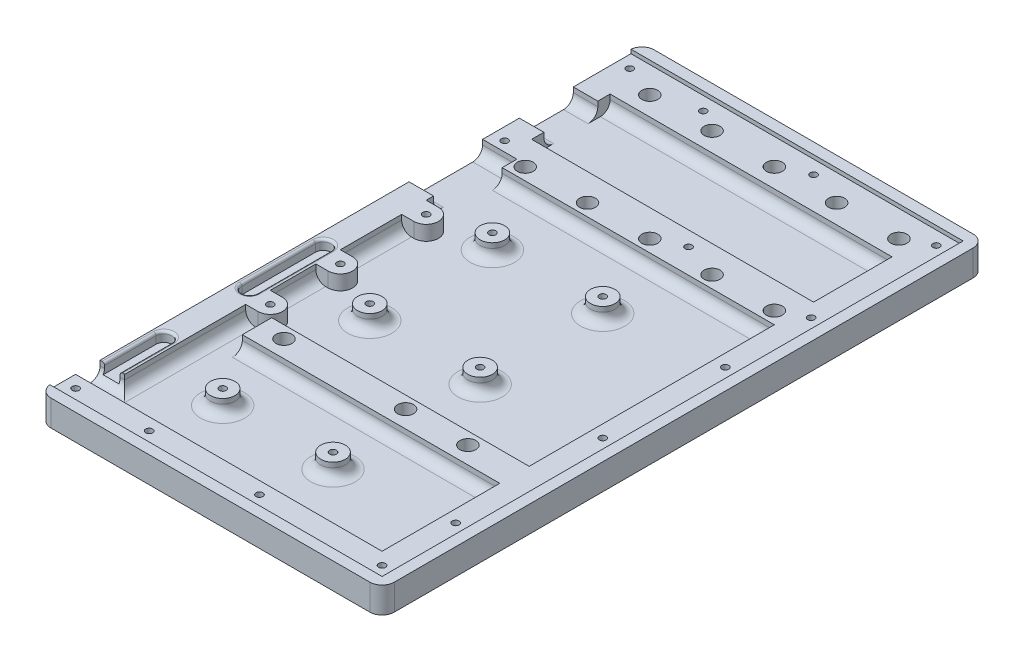
SolidWorks part; units mm, degrees
ref_plane "Front Plane" through (0, 0, 0) normal (0, 0, 1) x (1, 0, 0)
ref_plane "Top Plane" through (0, 0, 0) normal (0, 1, 0) x (1, 0, 0)
ref_plane "Right Plane" through (0, 0, 0) normal (1, 0, 0) x (0, 0, -1)
sketch "Sketch1" plane through (0, 0, 0) normal (0, 1, 0) x (1, 0, 0)
  line L1 (0, 0) -> (135, 0) construction
  line L2 (0, 0) -> (0, -236) construction
  line L3 (0, -236) -> (135, -236) construction
  line L4 (135, 0) -> (135, -236) construction
  line L8 (-0.5, 0.5) -> (-0.5, -236.5)
  line L9 (-0.5, -236.5) -> (135.5, -236.5)
  line L10 (135.5, 0.5) -> (135.5, -236.5)
  line L11 (-0.5, 0.5) -> (135.5, 0.5)
  line L13 (140, -241) -> (0, -241)
  line L14 (140, -241) -> (140, 5)
  line L15 (140, 5) -> (0, 5)
  line L16 (0, -241) -> (0, 5)
  dimension "D1" = 135
  dimension "D2" = 236
  dimension "D5" = 5
  dimension "D3" = 5
  dimension "D6" = 5
  dimension "D7" = 0
  dimension "D4" = 0.5
extrude "Boss-Extrude1" add sketch "Sketch1" along normal blind 1.6 contours L16 L13 L14 L15 L11 L10 L9 region at (2.8305, 0, -2.75)
sketch "Sketch2" plane through (0, 0, 0) normal (0, 1, 0) x (1, 0, 0)
  line L1 (10, -50) -> (125, -50)
  line L2 (10, -50) -> (10, -60)
  line L3 (10, -60) -> (125, -60)
  line L8 (0, 0) -> (135, 0) construction
  line L9 (10, -18) -> (125, -18)
  line L10 (10, -18) -> (10, -226)
  line L11 (10, -226) -> (125, -226)
  line L12 (125, -18) -> (125, -226)
  line L13 (125, -50) -> (125, -60)
  line L14 (0, -236) -> (135, -236) construction
  line L15 (0, 0) -> (0, -236) construction
  line L16 (-0.5, 0.5) -> (-0.5, -236.5) construction
  line L17 (140, 5) -> (0, 5)
  line L18 (140, 5) -> (140, -241)
  line L19 (140, -241) -> (0, -241)
  line L20 (0, 5) -> (0, -241)
  line L21 (-4.176, -226) -> (19.5, -226)
  line L22 (-4.176, -226) -> (-4.176, -216)
  line L23 (-4.176, -216) -> (19.5, -216)
  line L24 (19.5, -226) -> (19.5, -216)
  line L25 (17.2807, -23) -> (-10.9567, -23)
  line L26 (-7.239, -60) -> (13.5, -60)
  line L27 (-7.239, -60) -> (-7.239, -90)
  line L28 (-7.239, -90) -> (13.5, -90)
  line L29 (13.5, -60) -> (13.5, -90)
  line L30 (125, -166) -> (20, -166)
  line L31 (125, -166) -> (125, -178)
  line L32 (125, -178) -> (20, -178)
  line L33 (20, -166) -> (20, -178)
  line L34 (17.2807, -23) -> (17.2807, -45)
  line L35 (17.2807, -45) -> (-10.9567, -45)
  line L36 (-10.9567, -23) -> (-10.9567, -45)
  line L37 (14, -60) -> (125, -60)
  line L38 (14, -60) -> (14, -66)
  line L39 (14, -66) -> (125, -66)
  line L40 (125, -60) -> (125, -66)
  point P34 (3.1305, -60)
  dimension "D1" = 18
  dimension "D2" = 10
  dimension "D3" = 10
  dimension "D4" = 10
  dimension "D5" = 10
  dimension "D6" = 20
  dimension "D7" = 60
  dimension "D8" = 30
  dimension "D9" = 14
  dimension "D11" = 166
  dimension "D12" = 20
  dimension "D13" = 0
  dimension "D14" = 50
  dimension "D15" = 10
  dimension "D16" = 23
  dimension "D17" = 45
  dimension "D18" = 14
  dimension "D19" = 66
  dimension "D20" = 178
extrude "Boss-Extrude2" add sketch "Sketch2" against normal blind 6 contours L31 L32 L12 L11 L21 L20 L19 L18 L17 L25 L10 L9 L30 | L10 L35 L20 L26 L2 | L12 L1 L2 L3 | L28 L20 L23 L10 | L30 L33 L32 L12 | L31 L30 L33 L32 | L38 L37 L40 L39 region at (67.5, 0, 55) region at (5, 0, 52.5) region at (127.8305, 0, 34) region at (5, 0, 153) region at (72.5, 0, 172)
sketch "Sketch3" plane through (0, -6, 0) normal (0, -1, 0) x (1, 0, 0)
  line L1 (0, 241) -> (140, 241)
  line L2 (0, 241) -> (0, -5)
  line L3 (0, -5) -> (140, -5)
  line L4 (140, 241) -> (140, -5)
extrude "Boss-Extrude3" add sketch "Sketch3" along normal blind 3
sketch "Sketch4" plane through (0, 0, 0) normal (0, 1, 0) x (1, 0, 0)
  line L0 (0, 0) -> (135, 0) construction
  line L1 (0, -241) -> (0, 5) construction
  line L2 (135, 0) -> (135, -236) construction
  line L3 (0, -236) -> (135, -236) construction
  circle A0 centre (5, -5) radius 1.4
  circle A1 centre (35, -5) radius 1.4
  circle A2 centre (80, -5) radius 1.4
  circle A3 centre (130, -5) radius 1.4
  circle A4 centre (5, -231) radius 1.4
  circle A7 centre (130, -201) radius 1.4
  circle A8 centre (130, -56) radius 1.4
  circle A9 centre (130, -141) radius 1.4
  circle A10 centre (130, -91) radius 1.4
  circle A11 centre (80, -56) radius 1.4
  circle A12 centre (5, -56) radius 1.4
  circle A13 centre (130, -231) radius 1.4
  circle A14 centre (35, -231) radius 1.4
  circle A15 centre (80, -231) radius 1.4
  dimension "D1" = 5
  dimension "D3" = 30
  dimension "D4" = 5
  dimension "D6" = 5
  dimension "D7" = 130
  dimension "D10" = 80
  dimension "D14" = 231
  dimension "D15" = 80
  dimension "D2" = 5
  dimension "D5" = 45
  dimension "D8" = 141
  dimension "D9" = 56
  dimension "D11" = 5
  dimension "D12" = 91
  dimension "D13" = 201
  dimension "D16" = 35
extrude "Cut-Extrude1" cut sketch "Sketch4" against normal up to surface (6 mm away) up to face at (42, -6, 143.1429)
sketch "Sketch5" plane through (0, 0, 0) normal (0, 1, 0) x (1, 0, 0)
  line L0 (0, -241) -> (0, 5) construction
  line L1 (0, 0) -> (135, 0) construction
  line L3 (10, -90) -> (10, -216) construction
  line L8 (10, -90) -> (10, -216) construction
  line L9 (15, -93) -> (10, -93)
  line L10 (15, -93) -> (15, -103)
  line L11 (15, -103) -> (10, -103)
  line L12 (10, -93) -> (10, -103)
  line L14 (15, -138) -> (10, -138)
  line L15 (15, -138) -> (15, -128)
  line L16 (15, -128) -> (10, -128)
  line L17 (10, -138) -> (10, -128)
  line L18 (15, -166.6) -> (10, -166.6)
  line L19 (15, -166.6) -> (15, -156.6)
  line L20 (15, -156.6) -> (10, -156.6)
  line L21 (10, -166.6) -> (10, -156.6)
  circle A0 centre (35, -201) radius 1.4
  circle A4 centre (80, -201) radius 1.4
  circle A6 centre (35, -91) radius 1.4
  circle A7 centre (130, -91) radius 1.4 construction
  circle A8 centre (80, -91) radius 1.4
  circle A9 centre (35, -141) radius 1.4
  circle A11 centre (80, -141) radius 1.4
  circle A13 centre (15, -98) radius 1.4
  circle A14 centre (15, -161.6) radius 1.4
  circle A15 centre (15, -133) radius 1.4
  circle A16 centre (35, -201) radius 5
  circle A17 centre (80, -201) radius 5
  circle A18 centre (15, -98) radius 5
  circle A20 centre (15, -133) radius 5
  circle A21 centre (35, -91) radius 5
  circle A22 centre (80, -91) radius 5
  circle A23 centre (80, -141) radius 5
  circle A24 centre (35, -141) radius 5
  circle A25 centre (15, -161.6) radius 5
  dimension "D2" = 98
  dimension "D3" = 91
  dimension "D4" = 0
  dimension "D5" = 133
  dimension "D8" = 10
  dimension "D9" = 35
  dimension "D12" = 5
  dimension "D13" = 5
  dimension "D16" = 5
  dimension "D17" = 161.6
  dimension "D18" = 91
  dimension "D19" = 80
  dimension "D20" = 141
  dimension "D7" = 10
  dimension "D10" = 15
  dimension "D11" = 15
  dimension "D14" = 10
  dimension "D21" = 201
extrude "Boss-Extrude4" add sketch "Sketch5" against normal up to surface (6 mm away) contours A22 A8 | A17 A4 | A16 A0 | A21 A6 | A24 A9 | A23 A11 | A25 L21 L18 | L19 A25 A14 | L19 A25 A14 | A25 L20 L21 | L10 A18 A13 | L10 A18 A13 | A18 L12 L11 | A18 L9 L12 | A20 L16 L17 | L15 A20 A15 | A20 L17 L14 | L15 A20 A15 up to face at (42, -6, 143.1429)
sketch "Sketch6" plane through (0, 0, 0) normal (0, 1, 0) x (1, 0, 0)
  line L0 (5, -195) -> (5, -220) construction
  line L5 (8.2, -195) -> (8.2, -220)
  line L6 (1.8, -195) -> (1.8, -220)
  line L7 (0, -241) -> (0, 5) construction
  line L9 (5, -130) -> (5, -160) construction
  line L10 (8.2, -130) -> (8.2, -160)
  line L11 (1.8, -130) -> (1.8, -160)
  line L12 (0, 0) -> (135, 0) construction
  arc A0 (8.2, -195) -> (1.8, -195) centre (5, -195) ccw
  arc A1 (1.8, -220) -> (8.2, -220) centre (5, -220) ccw
  arc A2 (8.2, -130) -> (1.8, -130) centre (5, -130) ccw
  arc A3 (1.8, -160) -> (8.2, -160) centre (5, -160) ccw
  point P2 (5, -207.5)
  point P13 (5, -145)
  dimension "D4" = 130
  dimension "D1" = 5
  dimension "D2" = 195
  dimension "D3" = 25
  dimension "D5" = 160
  dimension "D6" = 1.8
  dimension "D7" = 1.8
extrude "Cut-Extrude2" cut sketch "Sketch6" against normal blind 4
sketch "Sketch7" plane through (0, -6, 0) normal (0, 1, 0) x (1, 0, 0)
  line L0 (0, -226) -> (125, -226) construction
  line L1 (0, -216) -> (14, -216)
  line L2 (0, -216) -> (0, -226)
  line L3 (0, -226) -> (14, -226)
  line L4 (14, -216) -> (14, -226)
  dimension "D1" = 14
sketch "Sketch11" plane through (0, 0, 0) normal (0, 1, 0) x (1, 0, 0)
  line L0 (0, 0) -> (135, 0) construction
  line L1 (0, -241) -> (0, 5) construction
  circle A0 centre (18.4, -10.2) radius 3.25
  dimension "D1" = 10.2
  dimension "D2" = 18.4
extrude "Cut-Extrude5" cut sketch "Sketch11" against normal through all
pattern_linear "LPattern1" count 5 spacing 25.4 along (1, 0, 0) count 2 spacing 50.8 along (0, 0, 1) of "Cut-Extrude5"
sketch "Sketch12" plane through (0, 0, 0) normal (0, 1, 0) x (1, 0, 0)
  line L0 (0, 0) -> (135, 0) construction
  line L1 (0, -241) -> (0, 5) construction
  circle A0 centre (105, -171) radius 3.25
  circle A1 centre (30, -171) radius 3.25
  circle A2 centre (79.6, -171) radius 3.25
  dimension "D1" = 171
  dimension "D3" = 30
  dimension "D2" = 105
  dimension "D4" = 25.4
extrude "Cut-Extrude6" cut sketch "Sketch12" against normal blind 10
fillet "Fillet1" radius 4 23 edges at (62.5, -6, 226) (72.5, -6, 166) (125, -6, 202) (72.5, -6, 178) (125, -6, 34) (125, -6, 116) (67.5, -6, 18) (5, -6, 90) (80, -6, 196) (80, -6, 86) (80, -6, 136) (35, -6, 136) (35, -6, 86) (35, -6, 196) (10, -6, 191.3) (10, -6, 147.3) (10, -6, 115.5) (69.5, -6, 66) (7, -6, 60) (67.5, -6, 50) (5, -6, 45) (5, -6, 23) (5, -6, 216)
fillet "Fillet2" radius 1 7 edges at (8.2, 0, 205.5) (1.8, 0, 205.5) (8.2, 0, 145) (5, 0, 163.2) (1.8, 0, 145) (5, 0, 191.8) (5, 0, 126.8)
fillet "Fillet3" radius 5 4 edges at (140, -3.7, -5) (140, -3.7, 241) (0, -3.7, 241) (0, -3.7, -5)
